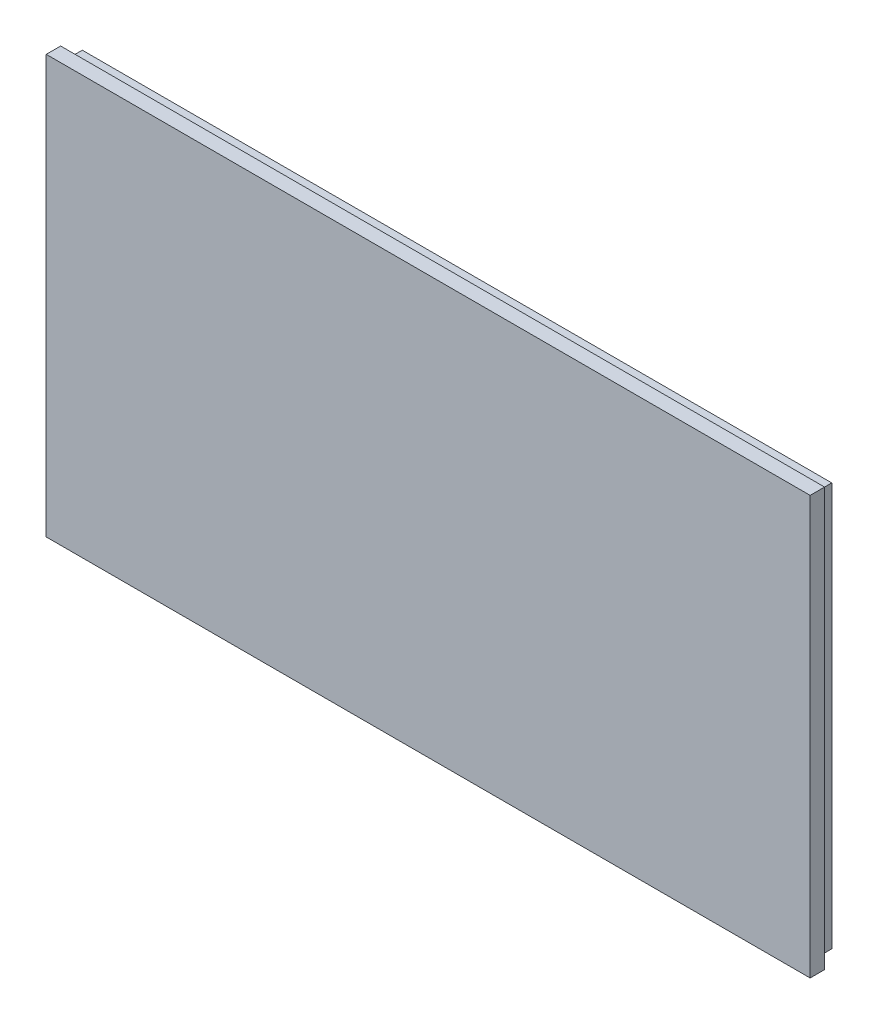
SolidWorks part; units mm, degrees
ref_plane "Front Plane" through (0, 0, 0) normal (0, 0, 1) x (1, 0, 0)
ref_plane "Top Plane" through (0, 0, 0) normal (0, 1, 0) x (1, 0, 0)
ref_plane "Right Plane" through (0, 0, 0) normal (1, 0, 0) x (0, 0, -1)
sketch "Sketch1" plane through (0, 0, 0) normal (0, 0, 1) x (1, 0, 0)
  line L1 (-26.5, -14.5) -> (26.5, -14.5)
  line L2 (-26.5, -14.5) -> (-26.5, 14.5)
  line L3 (-26.5, 14.5) -> (26.5, 14.5)
  line L4 (26.5, -14.5) -> (26.5, 14.5)
  line L5 (-26.5, -14.5) -> (26.5, 14.5) construction
  line L6 (-26.5, 14.5) -> (26.5, -14.5) construction
  point P0 (0, 0)
  dimension "D1" = 29
  dimension "D2" = 53
extrude "Boss-Extrude1" add sketch "Sketch1" along normal blind 1
sketch "Sketch2" plane through (0, 0, 0) normal (0, 0, -1) x (-1, 0, 0)
  line L1 (-26, -14) -> (26, -14)
  line L2 (-26, -14) -> (-26, 14)
  line L3 (-26, 14) -> (26, 14)
  line L4 (26, -14) -> (26, 14)
  line L5 (-26, -14) -> (26, 14) construction
  line L6 (-26, 14) -> (26, -14) construction
  point P0 (0, 0)
  dimension "D1" = 28
  dimension "D2" = 52
extrude "Boss-Extrude2" add sketch "Sketch2" along normal blind 1
shell "Shell1" thickness 1 removed face at (0, 0, -1)
